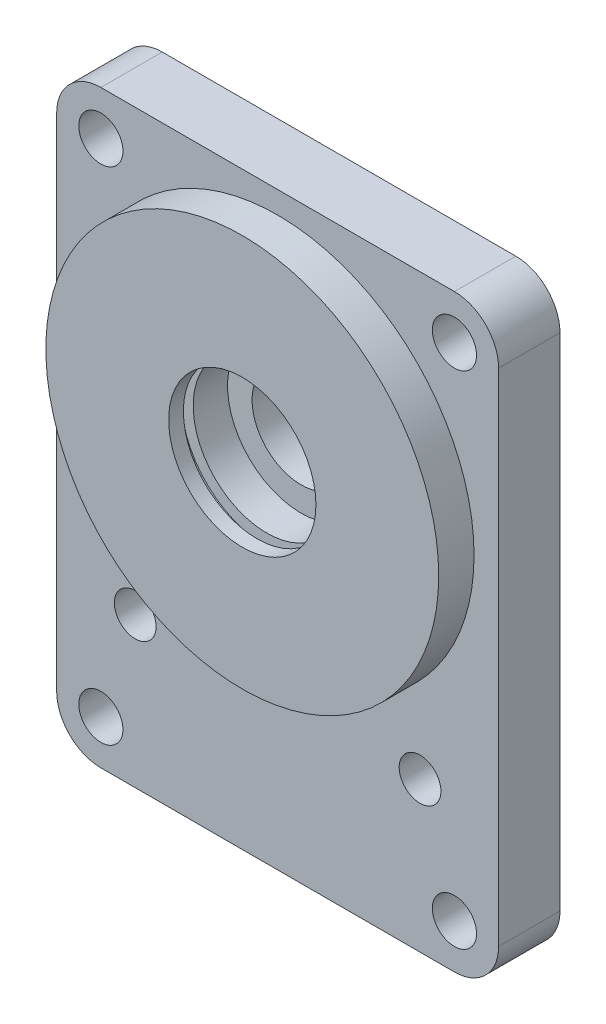
SolidWorks part; units mm, degrees
material "Gray Cast Iron"
ref_plane "Ebene vorne" through (0, 0, 0) normal (0, 0, 1) x (1, 0, 0)
ref_plane "Ebene oben" through (0, 0, 0) normal (0, 1, 0) x (1, 0, 0)
ref_plane "Ebene rechts" through (0, 0, 0) normal (1, 0, 0) x (0, 0, -1)
sketch "Sketch1" plane through (0, 0, 0) normal (0, 0, 1) x (1, 0, 0)
  line L0 (55, 0) -> (-55, 0) construction
  line L1 (-36, 60) -> (36, 60)
  line L2 (-45, 51) -> (-45, -51)
  line L3 (-36, -60) -> (36, -60)
  line L4 (45, 51) -> (45, -51)
  line L5 (-45, 60) -> (45, -60) construction
  line L6 (-45, -60) -> (45, 60) construction
  line L7 (0, -55) -> (0, 55) construction
  arc A0 (36, -60) -> (45, -51) centre (36, -51) ccw
  arc A1 (36, 60) -> (45, 51) centre (36, 51) cw
  arc A2 (-36, 60) -> (-45, 51) centre (-36, 51) ccw
  arc A3 (-45, -51) -> (-36, -60) centre (-36, -51) ccw
  circle A4 centre (-36, 51) radius 4.5
  circle A5 centre (-36, -51) radius 4.5
  circle A6 centre (36, 51) radius 4.5
  circle A7 centre (36, -51) radius 4.5
  point P0 (0, 0)
  dimension "D3" = 9
  dimension "D4" = 9
  dimension "D1" = 120
  dimension "D2" = 90
extrude "Boss-Extrude1" add sketch "Sketch1" along normal blind 12.5
sketch "Sketch2" plane through (0, 0, 12.5) normal (0, 0, 1) x (1, 0, 0)
  line L0 (0, 0) -> (0, 50.7491) construction
  circle A0 centre (0, 15.5) radius 40
  dimension "D2" = 80
  dimension "D1" = 15.5
extrude "Boss-Extrude2" add sketch "Sketch2" along normal blind 7.2
sketch "Sketch3" plane through (0, 0, 19.7) normal (0, 0, 1) x (1, 0, 0)
  circle A0 centre (0, 15.5) radius 10
  dimension "D1" = 20
extrude "Cut-Extrude1" cut sketch "Sketch3" against normal through all
sketch "Sketch5" plane through (0, 0, 0) normal (0, 0, -1) x (-1, 0, 0)
  line L0 (0, -57.2441) -> (0, 57.2441) construction
  line L1 (-40.2308, 29.5) -> (-40.2308, 27.2443)
  line L2 (-40.5173, 26.3626) -> (-42, 24.3219)
  line L3 (-42, 24.3219) -> (-42, -24.3219)
  line L4 (42, 24.3219) -> (42, -24.3219)
  line L5 (40.2308, 29.5) -> (40.2308, 27.2443)
  line L6 (40.5173, 26.3626) -> (42, 24.3219)
  line L7 (-40.5173, 26.3626) -> (-42, 24.3219)
  line L8 (-40.2308, 29.5) -> (-40.2308, 27.2443)
  line L9 (-42, 24.3219) -> (-42, -24.3219)
  line L10 (42, 24.3219) -> (42, -24.3219)
  line L11 (40.5173, 26.3626) -> (42, 24.3219)
  line L12 (40.2308, 29.5) -> (40.2308, 27.2443)
  line L13 (10.835, 0) -> (-10.835, 0) construction
  line L14 (40.2308, -29.5) -> (40.2308, -27.2443)
  line L15 (40.5173, -26.3626) -> (42, -24.3219)
  line L16 (-40.2308, -29.5) -> (-40.2308, -27.2443)
  line L17 (-40.5173, -26.3626) -> (-42, -24.3219)
  line L18 (40.5173, -26.3626) -> (42, -24.3219)
  line L19 (40.2308, -29.5) -> (40.2308, -27.2443)
  line L20 (-40.5173, -26.3626) -> (-42, -24.3219)
  line L21 (-40.2308, -29.5) -> (-40.2308, -27.2443)
  arc A0 (29, 40.7308) -> (-27.8978, 41.4935) centre (0, 0) ccw
  circle A1 centre (-29, 29.5) radius 5 construction
  arc A2 (-30.1677, 40.6699) -> (-40.2308, 29.5) centre (-29, 29.5) ccw
  arc A3 (-40.2308, 27.2443) -> (-40.5173, 26.3626) centre (-41.7308, 27.2443) cw
  arc A4 (-27.8978, 41.4935) -> (-30.1677, 40.6699) centre (-30.6876, 45.6428) cw
  circle A5 centre (29, 29.5) radius 5 construction
  arc A6 (40.2308, 27.2443) -> (40.5173, 26.3626) centre (41.7308, 27.2443) ccw
  arc A7 (30.1677, 40.6699) -> (40.2308, 29.5) centre (29, 29.5) cw
  arc A8 (27.8978, 41.4935) -> (30.1677, 40.6699) centre (30.6876, 45.6428) ccw
  arc A9 (-27.8978, 41.4935) -> (-30.1677, 40.6699) centre (-30.6876, 45.6428) cw
  arc A10 (-30.1677, 40.6699) -> (-40.2308, 29.5) centre (-29, 29.5) ccw
  arc A11 (-40.2308, 27.2443) -> (-40.5173, 26.3626) centre (-41.7308, 27.2443) cw
  circle A12 centre (-29, 29.5) radius 5 construction
  arc A13 (27.8978, 41.4935) -> (30.1677, 40.6699) centre (30.6876, 45.6428) ccw
  arc A14 (40.2308, 27.2443) -> (40.5173, 26.3626) centre (41.7308, 27.2443) ccw
  arc A15 (30.1677, 40.6699) -> (40.2308, 29.5) centre (29, 29.5) cw
  circle A16 centre (29, 29.5) radius 5 construction
  arc A17 (-29, 40.7308) -> (27.8978, 41.4935) centre (0, 0) cw
  arc A18 (-29, -40.7308) -> (27.8978, -41.4935) centre (0, 0) ccw
  circle A19 centre (29, -29.5) radius 5 construction
  arc A20 (30.1677, -40.6699) -> (40.2308, -29.5) centre (29, -29.5) ccw
  arc A21 (40.2308, -27.2443) -> (40.5173, -26.3626) centre (41.7308, -27.2443) cw
  arc A22 (27.8978, -41.4935) -> (30.1677, -40.6699) centre (30.6876, -45.6428) cw
  circle A23 centre (-29, -29.5) radius 5 construction
  arc A24 (-40.2308, -27.2443) -> (-40.5173, -26.3626) centre (-41.7308, -27.2443) ccw
  arc A25 (-30.1677, -40.6699) -> (-40.2308, -29.5) centre (-29, -29.5) cw
  arc A26 (-27.8978, -41.4935) -> (-30.1677, -40.6699) centre (-30.6876, -45.6428) ccw
  arc A27 (27.8978, -41.4935) -> (30.1677, -40.6699) centre (30.6876, -45.6428) cw
  arc A28 (30.1677, -40.6699) -> (40.2308, -29.5) centre (29, -29.5) ccw
  arc A29 (40.2308, -27.2443) -> (40.5173, -26.3626) centre (41.7308, -27.2443) cw
  circle A30 centre (29, -29.5) radius 5 construction
  arc A31 (-27.8978, -41.4935) -> (-30.1677, -40.6699) centre (-30.6876, -45.6428) ccw
  arc A32 (-40.2308, -27.2443) -> (-40.5173, -26.3626) centre (-41.7308, -27.2443) ccw
  arc A33 (-30.1677, -40.6699) -> (-40.2308, -29.5) centre (-29, -29.5) cw
  circle A34 centre (-29, -29.5) radius 5 construction
  arc A35 (29, -40.7308) -> (-27.8978, -41.4935) centre (0, 0) cw
  point P16 (-29, 40.7308)
  point P20 (-42, 0)
  point P58 (42, 0)
  circle M11 centre (0, 15.5) radius 10
  dimension "D1" = 50
  dimension "D4" = 10
  dimension "D6" = 1.5
  dimension "D7" = 5
  dimension "D2" = 29
  dimension "D3" = 29.5
  dimension "D5" = 42
extrude "Boss-Extrude3" add sketch "Sketch5" along normal blind 3 contours A26 A18 A22 A20 L14 A21 L15 L4 L6 A6 L5 A7 A8 A0 A4 A2 L1 A3 L2 L3 L17 A24 L16 A25 A30 A34 M11 region at (0, -0.6912, 0)
hole_wizard "M10 Tapped Hole1" positions "Sketch7" profile "Sketch8" tap size "M10" standard "ISO"
sketch "Sketch7" plane through (0, 0, -3) normal (0, 0, -1) x (-1, 0, 0)
  point P0 (-29, 29.5)
  point P2 (-29, -29.5)
  point P4 (29, -29.5)
  point P6 (29, 29.5)
  dimension "D1" = 58
  dimension "D2" = 59
  dimension "D3" = 29.5
  dimension "D4" = 29
sketch "Sketch8" plane through (29, 29.5, -3) normal (1, 0, 0) x (0, 1, 0)
  line L0 (0, 0) -> (0, 19.5537)
  line L1 (0, 19.5537) -> (4.25, 17)
  line L2 (4.25, 17) -> (4.25, 0.775)
  line L3 (4.25, 0.775) -> (5.025, 0)
  line L5 (5.025, 0) -> (0, 0)
  line L6 (-4.25, 0.775) -> (-5.025, 0) construction
  line L10 (0, 19.5537) -> (-4.25, 17) construction
  line L11 (0, -6.35) -> (0, 107.95) construction
  dimension "Tap Drill Dia." = 8.5
  dimension "Tap Drill Depth" = 17
  dimension "Near C'Sink Dia." = 10.05
  dimension "Near C'Sink Angle" = 90
  dimension "Drill Angle" = 118
cosmetic thread "Hole Thread1" parameters "D1"=20, "D2"=10
cosmetic thread "Hole Thread2" parameters "D1"=20, "D2"=10
cosmetic thread "Hole Thread3" parameters "D1"=20, "D2"=10
cosmetic thread "Hole Thread4" parameters "D1"=20, "D2"=10
sketch "Sketch10" plane through (0, 0, 0) normal (0, 0, -1) x (-1, 0, 0)
  circle A0 centre (-36, 51) radius 8
  circle A1 centre (36, 51) radius 8
  circle A2 centre (36, -51) radius 8
  circle A3 centre (-36, -51) radius 8
  dimension "D1" = 16
extrude "Cut-Extrude3" cut sketch "Sketch10" against normal blind 0.5
sketch "Sketch11" plane through (0, 0, 19.7) normal (0, 0, 1) x (1, 0, 0)
  circle A0 centre (0, 15.5) radius 15
  dimension "D1" = 30
extrude "Cut-Extrude4" cut sketch "Sketch11" against normal blind 12
sketch "Sketch12" plane through (0, 0, 0) normal (1, 0, 0) x (0, 0, -1)
  line L1 (-16.7, 32.9188) -> (-14.7, 32.9188)
  line L2 (-16.7, 32.9188) -> (-16.7, 27.9188)
  line L3 (-16.7, 27.9188) -> (-14.7, 27.9188)
  line L4 (-14.7, 32.9188) -> (-14.7, 27.9188)
  line L5 (-16.7, 32.9188) -> (-14.7, 27.9188) construction
  line L6 (-16.7, 27.9188) -> (-14.7, 32.9188) construction
  line L7 (-19.7, 55.5) -> (-19.7, -24.5) construction
  point P0 (-15.7, 30.4188)
  dimension "D1" = 5
  dimension "D2" = 2
  dimension "D3" = 3
revolve "Cut-Revolve1" cut sketch "Sketch12" angle 360 about axis through (0, 15.5, 19.7) along (0, 0, -1)
hole_wizard "Tap Drill for M4 Tap1" positions "Sketch13" profile "Sketch14" hole size "M4" standard "ISO"
sketch "Sketch13" plane through (0, 0, -3) normal (0, 0, -1) x (-1, 0, 0)
  point P0 (0, 45)
  point P2 (0, -45)
  dimension "D1" = 45
  dimension "D2" = 45
sketch "Sketch14" plane through (0, 45, -3) normal (1, 0, 0) x (0, 1, 0)
  line L0 (0, 0) -> (0, 3.9914)
  line L1 (0, 3.9914) -> (1.65, 3)
  line L2 (1.65, 3) -> (1.65, 0.025)
  line L3 (1.65, 0.025) -> (1.675, 0)
  line L5 (1.675, 0) -> (0, 0)
  line L6 (-1.65, 0.025) -> (-1.675, 0) construction
  line L10 (0, 3.9914) -> (-1.65, 3) construction
  line L11 (0, -6.35) -> (0, 107.95) construction
  dimension "Hole Dia." = 3.3
  dimension "Hole Depth" = 3
  dimension "Near C'Sink Dia." = 3.35
  dimension "Near C'Sink Angle" = 90
  dimension "Drill Angle" = 118
